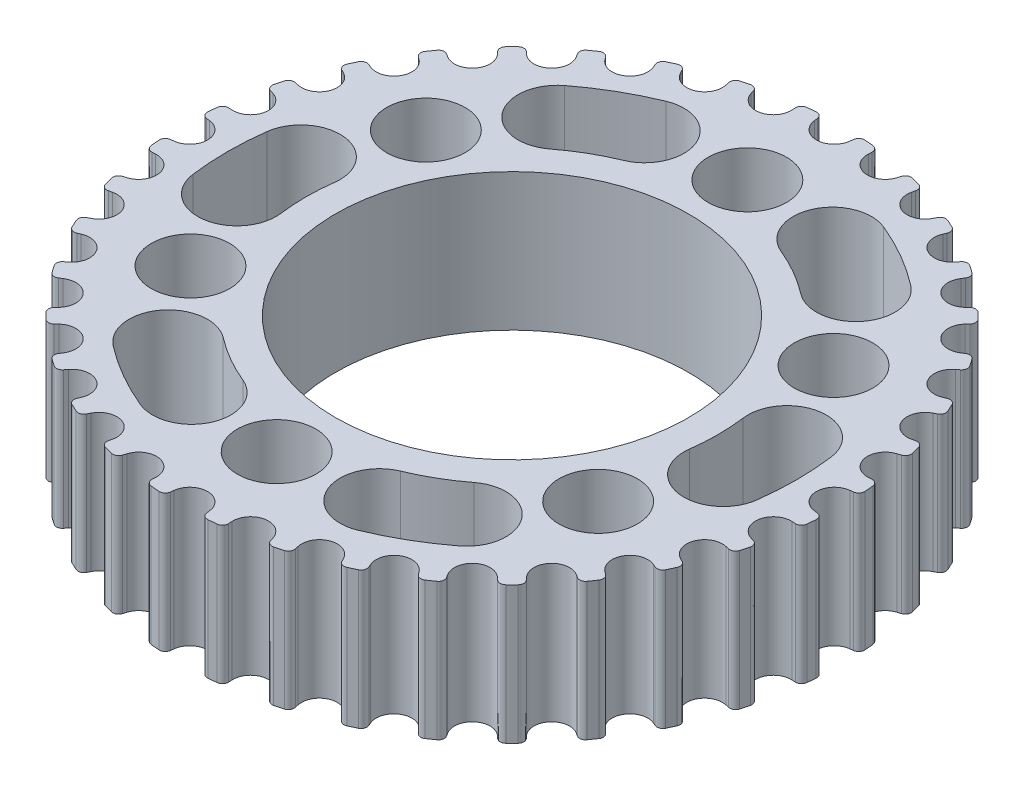
SolidWorks part; units mm, degrees
material "6061 合金"
ref_plane "前视基准面" through (0, 0, 0) normal (0, 0, 1) x (1, 0, 0)
ref_plane "上视基准面" through (0, 0, 0) normal (0, 1, 0) x (1, 0, 0)
ref_plane "右视基准面" through (0, 0, 0) normal (1, 0, 0) x (0, 0, -1)
ref_axis "基准轴1" through (0, -44, 0) along (0, 1, 0)
sketch "草图1" plane through (0, 0, 0) normal (0, 1, 0) x (1, 0, 0)
  circle A0 centre (0, 0) radius 16.8
extrude "凸台-拉伸1" add sketch "草图1" along normal mid plane 7
sketch "草图2" plane through (0, 0, 0) normal (0, 1, 0) x (1, 0, 0)
  line B0 (-0.9032, 16.3191) -> (-0.9244, 16.4912)
  line B1 (0.9032, 16.3191) -> (0.9244, 16.4912)
  arc B2 (-0.9032, 16.3191) -> (0.9032, 16.3191) centre (0, 16.43) ccw
  arc B3 (-1.2443, 16.7539) -> (1.2443, 16.7539) centre (0, 0) cw
  arc B4 (-0.9244, 16.4912) -> (-1.2443, 16.7539) centre (-1.2221, 16.4547) ccw
  arc B5 (1.2443, 16.7539) -> (0.9244, 16.4912) centre (1.2221, 16.4547) ccw
sketch_block_instance "HTD-1"
sketch_block "HTD" parameters "OD"=33.6, "D4"=0.3, "Rb"=0.91, "Rt"=0.3, "Dh"=1.28, "deg"=14
extrude "切除-拉伸1" cut sketch "草图2" against normal mid plane 100
pattern_circular "阵列(圆周)1" count 36 over 360 about axis through (0, -44, 0) along (0, 1, 0) of "切除-拉伸1"
sketch "草图4" plane through (0, 0, 0) normal (0, 1, 0) x (1, 0, 0)
  circle A0 centre (0, 0) radius 9
  dimension "D1" = 18
extrude "切除-拉伸2" cut sketch "草图4" against normal mid plane 100
sketch "草图5" plane through (0, 3.5, 0) normal (0, 1, 0) x (1, 0, 0)
  line L0 (0, 0) -> (50000, 0) construction
  line L1 (0, 0) -> (0, 50000) construction
  line L2 (0, 0) -> (4.6558, 8.0641) construction
  circle A1 centre (0, 0) radius 12 construction
  circle A3 centre (0, 12) radius 2
  circle A4 centre (10.3923, 6) radius 2
  circle A5 centre (10.3923, -6) radius 2
  circle A6 centre (0, -12) radius 2
  circle A7 centre (-10.3923, -6) radius 2
  circle A8 centre (-10.3923, 6) radius 2
  point P19 (0, 0)
  point P31 (0, 0)
  dimension "D2" = 24
  dimension "D4" = 6
  dimension "D7" = 4
  dimension "D5" = 60
extrude "切除-拉伸4" cut sketch "草图5" against normal through all
sketch "草图6" plane through (0, 3.5, 0) normal (0, 1, 0) x (1, 0, 0)
  line L0 (0, 0) -> (22.6441, 0) construction
  line L1 (0, 0) -> (5.511, 13.3047) construction
  line L2 (0, 0) -> (8.7343, 11.3827) construction
  circle A0 centre (0, 0) radius 12.5 construction
  arc A1 (4.7835, 11.5485) -> (7.6095, 9.9169) centre (0, 0) cw construction
  arc A2 (8.827, 11.5036) -> (5.5489, 13.3963) centre (0, 0) ccw
  arc A3 (6.392, 8.3302) -> (4.0182, 9.7007) centre (0, 0) ccw
  arc A4 (6.392, 8.3302) -> (8.827, 11.5036) centre (7.6095, 9.9169) ccw
  arc A5 (5.5489, 13.3963) -> (4.0182, 9.7007) centre (4.7835, 11.5485) ccw
  arc A6 (12.3931, 1.6316) -> (12.3931, -1.6316) centre (0, 0) cw construction
  arc A7 (14.376, -1.8926) -> (14.376, 1.8926) centre (0, 0) ccw
  arc A8 (10.4102, -1.3705) -> (10.4102, 1.3705) centre (0, 0) ccw
  arc A9 (10.4102, -1.3705) -> (14.376, -1.8926) centre (12.3931, -1.6316) ccw
  arc A10 (14.376, 1.8926) -> (10.4102, 1.3705) centre (12.3931, 1.6316) ccw
  arc A11 (7.6095, -9.9169) -> (4.7835, -11.5485) centre (0, 0) cw construction
  arc A12 (5.5489, -13.3963) -> (8.827, -11.5036) centre (0, 0) ccw
  arc A13 (4.0182, -9.7007) -> (6.392, -8.3302) centre (0, 0) ccw
  arc A14 (4.0182, -9.7007) -> (5.5489, -13.3963) centre (4.7835, -11.5485) ccw
  arc A15 (8.827, -11.5036) -> (6.392, -8.3302) centre (7.6095, -9.9169) ccw
  arc A16 (-4.7835, -11.5485) -> (-7.6095, -9.9169) centre (0, 0) cw construction
  arc A17 (-8.827, -11.5036) -> (-5.5489, -13.3963) centre (0, 0) ccw
  arc A18 (-6.392, -8.3302) -> (-4.0182, -9.7007) centre (0, 0) ccw
  arc A19 (-6.392, -8.3302) -> (-8.827, -11.5036) centre (-7.6095, -9.9169) ccw
  arc A20 (-5.5489, -13.3963) -> (-4.0182, -9.7007) centre (-4.7835, -11.5485) ccw
  arc A21 (-12.3931, -1.6316) -> (-12.3931, 1.6316) centre (0, 0) cw construction
  arc A22 (-14.376, 1.8926) -> (-14.376, -1.8926) centre (0, 0) ccw
  arc A23 (-10.4102, 1.3705) -> (-10.4102, -1.3705) centre (0, 0) ccw
  arc A24 (-10.4102, 1.3705) -> (-14.376, 1.8926) centre (-12.3931, 1.6316) ccw
  arc A25 (-14.376, -1.8926) -> (-10.4102, -1.3705) centre (-12.3931, -1.6316) ccw
  arc A26 (-7.6095, 9.9169) -> (-4.7835, 11.5485) centre (0, 0) cw construction
  arc A27 (-5.5489, 13.3963) -> (-8.827, 11.5036) centre (0, 0) ccw
  arc A28 (-4.0182, 9.7007) -> (-6.392, 8.3302) centre (0, 0) ccw
  arc A29 (-4.0182, 9.7007) -> (-5.5489, 13.3963) centre (-4.7835, 11.5485) ccw
  arc A30 (-8.827, 11.5036) -> (-6.392, 8.3302) centre (-7.6095, 9.9169) ccw
  point P9 (6.25, 10.8253)
  point P18 (12.5, 0)
  point P25 (6.25, -10.8253)
  point P32 (-6.25, -10.8253)
  point P39 (-12.5, 0)
  point P46 (-6.25, 10.8253)
  point P51 (0, 0)
  dimension "D3" = 2
  dimension "D5" = 25
  dimension "D1" = 52.5
  dimension "D2" = 15
  dimension "D4" = 6
extrude "切除-拉伸5" cut sketch "草图6" against normal blind 10
